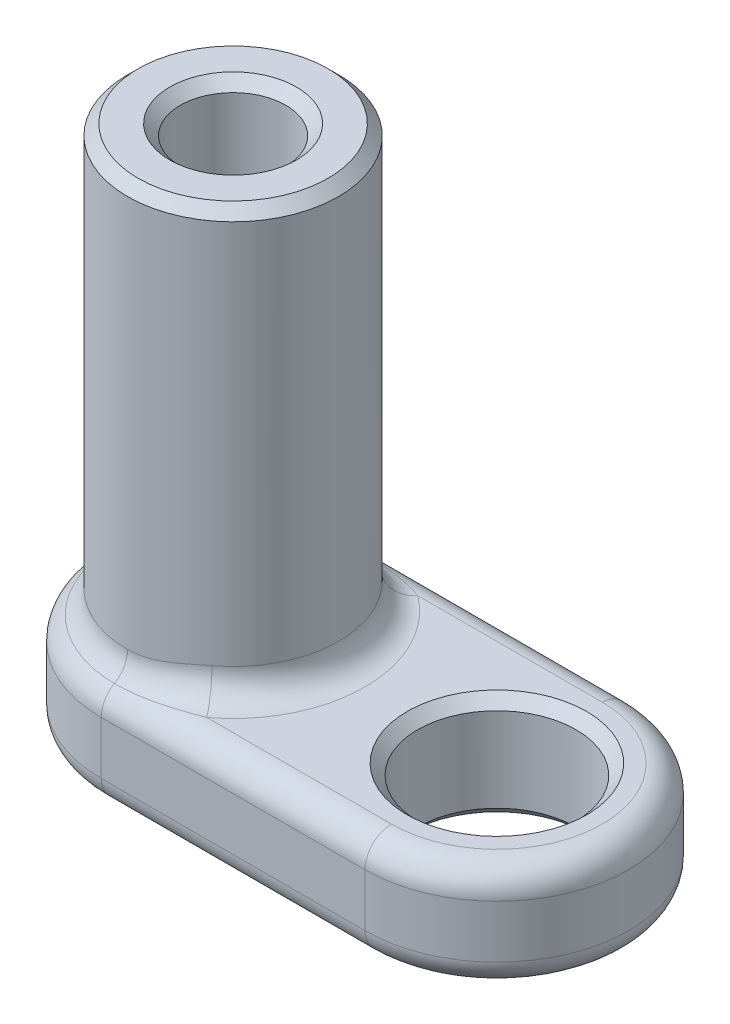
SolidWorks part; units mm, degrees
ref_plane "Front Plane" through (0, 0, 0) normal (0, 0, 1) x (1, 0, 0)
ref_plane "Top Plane" through (0, 0, 0) normal (0, 1, 0) x (1, 0, 0)
ref_plane "Right Plane" through (0, 0, 0) normal (1, 0, 0) x (0, 0, -1)
sketch "Sketch1" plane through (0, 0, 0) normal (0, 1, 0) x (1, 0, 0)
  circle A0 centre (0, 0) radius 20
  dimension "D1" = 40
extrude "Boss-Extrude1" add sketch "Sketch1" along normal blind 100
sketch "Sketch2" plane through (0, 0, 0) normal (0, -1, 0) x (1, 0, 0)
  line L0 (0, 0) -> (50, 0) construction
  line L1 (0, 25) -> (50, 25)
  line L2 (0, -25) -> (50, -25)
  arc A0 (0, 25) -> (0, -25) centre (0, 0) ccw
  arc A1 (50, -25) -> (50, 25) centre (50, 0) ccw
  point P3 (25, 0)
  dimension "D2" = 25
  dimension "D1" = 50
extrude "Boss-Extrude2" add sketch "Sketch2" against normal blind 20
hole_wizard "CBORE for M5 Hex Head Bolt1" positions "Sketch6" profile "Sketch7" counterbore size "M5" standard "ISO"
sketch "Sketch6" plane through (0, 0, 0) normal (0, -1, 0) x (-1, 0, 0)
  point P0 (0, 0)
sketch "Sketch7" plane through (0, 0, 0) normal (1, 0, 0) x (0, 0, -1)
  line L0 (0, 0) -> (0, 106.0086)
  line L1 (0, 106.0086) -> (10, 100)
  line L2 (10, 100) -> (10, 10)
  line L3 (10, 10) -> (16, 10)
  line L4 (16, 10) -> (16, 0)
  line L5 (16, 0) -> (0, 0)
  line L10 (0, 106.0086) -> (-10, 100) construction
  line L11 (0, -6.35) -> (0, 107.95) construction
  dimension "Hole Dia." = 20
  dimension "Hole Depth" = 100
  dimension "C'Bore Dia." = 32
  dimension "C'Bore Depth" = 10
  dimension "Drill Angle" = 118
hole_wizard "Ø1.5mm Dowel Hole1" positions "Sketch8" profile "Sketch9" hole size "Ø1.5" standard "ISO"
sketch "Sketch8" plane through (0, 0, 0) normal (0, -1, 0) x (1, 0, 0)
  point P0 (50, 0)
  dimension "D1" = 50
sketch "Sketch9" plane through (50, 0, 0) normal (1, 0, 0) x (0, 0, -1)
  line L0 (0, 0) -> (0, 109.0129)
  line L1 (0, 109.0129) -> (15, 100)
  line L2 (15, 100) -> (15, 0)
  line L5 (15, 0) -> (0, 0)
  line L10 (0, 109.0129) -> (-15, 100) construction
  line L11 (0, -6.35) -> (0, 107.95) construction
  dimension "Hole Dia." = 30
  dimension "Hole Depth" = 100
  dimension "Drill Angle" = 118
chamfer "Chamfer1" distance 2 angle 45 1 edges at (50, 20, -15)
chamfer "Chamfer2" distance 2 angle 45 1 edges at (50, 0, -15)
chamfer "Chamfer3" distance 2 angle 45 1 edges at (0, 100, -10)
chamfer "Chamfer4" distance 2 angle 45 1 edges at (0, 0, -16)
chamfer "Chamfer5" distance 2 angle 45 2 edges at (0, 10, -16) (0, 10, -10)
fillet "Fillet1" radius 5 8 edges at (-25, 0, 0) (25, 0, 25) (75, 0, 0) (-25, 20, 0) (25, 20, 25) (75, 20, 0) (25, 0, -25) (25, 20, -25)
fillet "Fillet2" radius 5 2 edges at (-20, 20, 0) (20, 20, 0)
chamfer "Chamfer6" distance 2 angle 45 1 edges at (0, 100, 20)
